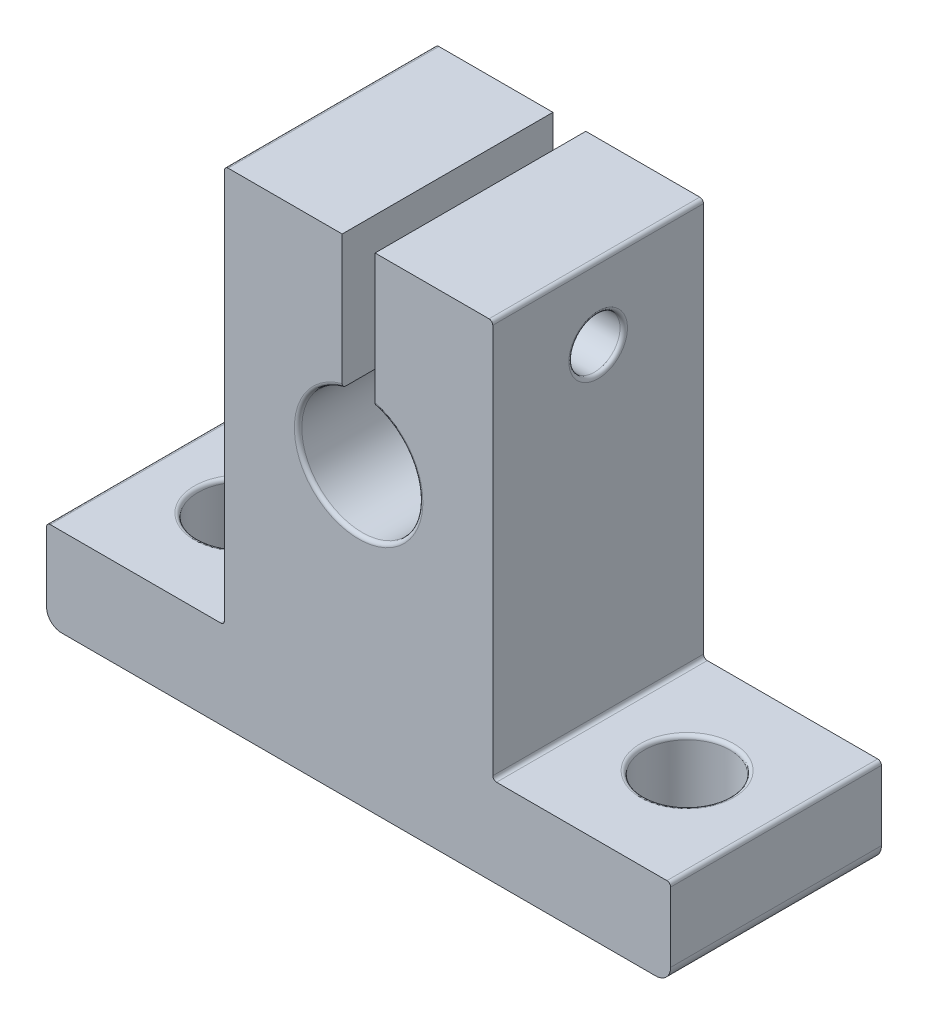
SolidWorks part; units mm, degrees
ref_plane "Front Plane" through (0, 0, 0) normal (0, 0, 1) x (1, 0, 0)
ref_plane "Top Plane" through (0, 0, 0) normal (0, 1, 0) x (1, 0, 0)
ref_plane "Right Plane" through (0, 0, 0) normal (1, 0, 0) x (0, 0, -1)
sketch "Sketch1" plane through (0, 0, 0) normal (0, 0, 1) x (1, 0, 0)
  line L0 (-20.875, 0) -> (20.875, 0)
  line L1 (20.875, 0) -> (20.875, 5.9)
  line L2 (20.875, 5.9) -> (8.975, 5.9)
  line L3 (8.975, 5.9) -> (8.975, 32.5)
  line L4 (8.975, 32.5) -> (1.1, 32.5)
  line L5 (1.1, 32.5) -> (1.1, 23.5728)
  line L6 (0, 0) -> (0, 19.675) construction
  line L7 (-1.1, 32.5) -> (-1.1, 23.5728)
  line L8 (-8.975, 32.5) -> (-1.1, 32.5)
  line L9 (-8.975, 5.9) -> (-8.975, 32.5)
  line L10 (-20.875, 5.9) -> (-8.975, 5.9)
  line L11 (-20.875, 0) -> (-20.875, 5.9)
  arc A0 (-1.1, 23.5728) -> (1.1, 23.5728) centre (0, 19.675) ccw
  dimension "D7" = 11.9
  dimension "D5" = 4.05
  dimension "D1" = 20.875
  dimension "D2" = 5.9
  dimension "D3" = 32.5
  dimension "D4" = 7.875
  dimension "D6" = 19.675
  dimension "D8" = 8.9272
extrude "Boss-Extrude1" add sketch "Sketch1" along normal mid plane 14.1
sketch "Sketch2" plane through (0, 5.9, 0) normal (0, 1, 0) x (1, 0, 0)
  line L0 (20.875, 0) -> (14.925, 0) construction
  line L1 (20.875, -7.05) -> (20.875, 7.05) construction
  line L2 (0, -7.755) -> (0, 7.755) construction
  circle A0 centre (14.925, 0) radius 2.875
  circle A1 centre (-14.925, 0) radius 2.875
  dimension "D2" = 5.75
  dimension "D1" = 5.95
extrude "Mounting Holes" cut sketch "Sketch2" against normal up to next
sketch "Sketch3" plane through (8.975, 0, 0) normal (1, 0, 0) x (0, 0, -1)
  line L0 (0, 32.5) -> (0, 27.59) construction
  line L1 (-7.05, 32.5) -> (7.05, 32.5) construction
  circle A0 centre (0, 27.59) radius 1.71
  dimension "D2" = 3.42
  dimension "D1" = 4.91
extrude "Bolt Hole" cut sketch "Sketch3" against normal through all
sketch "Sketch4" plane through (-8.975, 0, 0) normal (-1, 0, 0) x (0, 0, 1)
  circle A0 centre (0, 27.59) radius 3.675
  dimension "D1" = 7.35
extrude "Bolt Head" cut sketch "Sketch4" against normal blind 3.95
fillet "Holes" radius 0.25 5 edges at (8.975, 27.59, -1.71) (-12.05, 5.9, 0) (12.05, 5.9, 0) (0, 15.625, 7.05) (0, 15.625, -7.05)
sketch "Sketch5" plane through (-8.975, 0, 0) normal (-1, 0, 0) x (0, 0, 1)
  circle A5 centre (0, 27.59) radius 4.075
  circle A6 centre (0, 27.59) radius 4.075
  dimension "D1" = 0.4
extrude "Bolt Head Int Fillet" cut sketch "Sketch5" against normal blind 0.5 draft 45
fillet "Bottom Mounting" radius 0.5 2 edges at (14.925, 0, 2.875) (-14.925, 0, 2.875)
fillet "Bottom Corners" radius 1 2 edges at (20.875, 0, 0) (-20.875, 0, 0)
fillet "Corners" radius 0.25 6 edges at (8.975, 32.5, 0) (-8.975, 32.5, 0) (20.875, 5.9, 0) (8.975, 5.9, 0) (-8.975, 5.9, 0) (-20.875, 5.9, 0)
